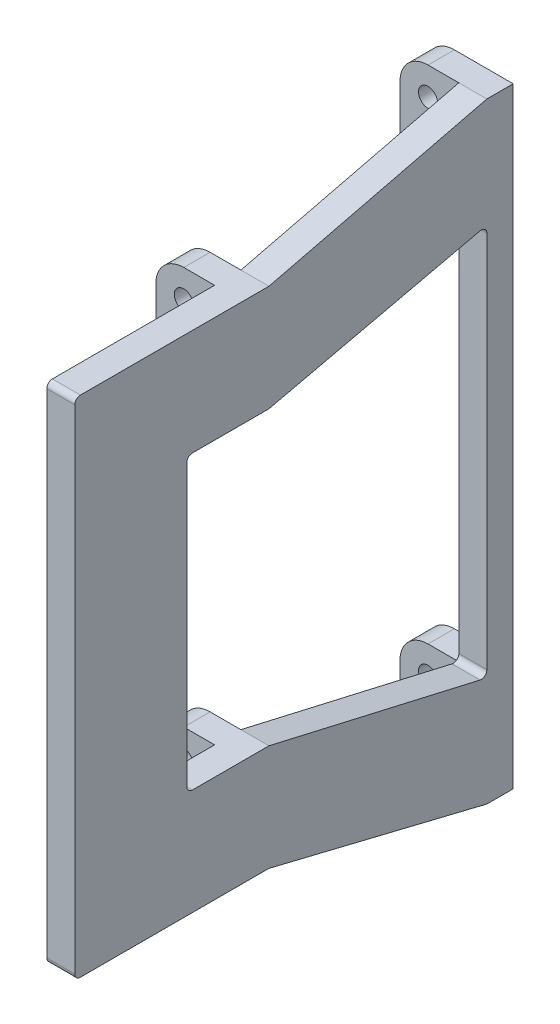
SolidWorks part; units mm, degrees
ref_plane "前基準面" through (0, 0, 0) normal (1, 0, 0) x (0, 1, 0)
ref_plane "上基準面" through (0, 0, 0) normal (0, 0, 1) x (0, 1, 0)
ref_plane "右基準面" through (0, 0, 0) normal (0, 1, 0) x (-1, 0, 0)
sketch "草圖1" plane through (0, 0, 0) normal (1, 0, 0) x (0, 1, 0)
  line L1 (-54.5, 39.125) -> (54.5, 39.125)
  line L2 (-54.5, 39.125) -> (-54.5, -39.125)
  line L3 (-54.5, -39.125) -> (54.5, -39.125)
  line L4 (54.5, 39.125) -> (54.5, -39.125)
  line L5 (-54.5, 39.125) -> (54.5, -39.125) construction
  line L6 (-54.5, -39.125) -> (54.5, 39.125) construction
  point P0 (0, 0)
  dimension "D1" = 78.25
  dimension "D2" = 109
extrude "填料-伸長1" add sketch "草圖1" along normal blind 5
sketch "草圖2" plane through (0, 0, 0) normal (-1, 0, 0) x (0, -1, 0)
  line L0 (-54.5, 39.125) -> (-54.5, -34.425)
  line L1 (-54.5, -39.125) -> (-54.5, 39.125) construction
  line L2 (-54.5, 39.125) -> (-45, 39.125)
  line L3 (-54.5, 39.125) -> (54.5, 39.125) construction
  line L4 (-45, 39.125) -> (-45, 4.475)
  line L5 (-45, 4.475) -> (-54.5, -34.425)
  line L6 (0, 39.125) -> (0, -39.125) construction
  line L7 (54.5, -39.125) -> (-54.5, -39.125) construction
  line L8 (45, 39.125) -> (45, 4.475)
  line L9 (54.5, 39.125) -> (45, 39.125)
  line L10 (54.5, 39.125) -> (54.5, -34.425)
  line L11 (45, 4.475) -> (54.5, -34.425)
  line L12 (-35, -34.425) -> (35, -34.425)
  line L13 (-26.05, 19.125) -> (26.05, 19.125)
  line L14 (-26.05, 19.125) -> (-26.05, 4.475)
  line L15 (26.05, 19.125) -> (26.05, 4.475)
  line L16 (-26.05, 4.475) -> (-35, -34.425)
  line L17 (26.05, 4.475) -> (35, -34.425)
  point P19 (0, -34.425)
  point P22 (0, 19.125)
  dimension "D1" = 73.55
  dimension "D2" = 9.5
  dimension "D3" = 34.65
  dimension "D4" = 70
  dimension "D5" = 4.7
  dimension "D6" = 52.1
  dimension "D7" = 20
  dimension "D8" = 14.65
  dimension "D9" = 14.65
extrude "除料-伸長1" cut sketch "草圖2" against normal blind 5
sketch "草圖3" plane through (0, 0, 0) normal (-1, 0, 0) x (0, -1, 0)
  line L0 (-26.05, 19.125) -> (-26.05, 4.475) construction
  line L1 (-45, 4.475) -> (-26.05, 4.475)
  line L2 (-45, 4.475) -> (-45, 9.175)
  line L3 (-45, 9.175) -> (-26.05, 9.175)
  line L4 (-26.05, 4.475) -> (-26.05, 9.175)
  line L5 (0, 39.125) -> (0, -39.125) construction
  line L6 (-54.5, -39.125) -> (-35, -39.125)
  line L7 (-54.5, -39.125) -> (-54.5, -34.425)
  line L8 (-54.5, -34.425) -> (-35, -34.425)
  line L9 (-35, -39.125) -> (-35, -34.425)
  line L10 (-45, 39.125) -> (45, 39.125) construction
  line L11 (54.5, -39.125) -> (-54.5, -39.125) construction
  line L12 (54.5, -34.425) -> (35, -34.425)
  line L13 (35, -39.125) -> (35, -34.425)
  line L14 (54.5, -39.125) -> (35, -39.125)
  line L15 (54.5, -39.125) -> (54.5, -34.425)
  line L16 (45, 9.175) -> (26.05, 9.175)
  line L17 (26.05, 4.475) -> (26.05, 9.175)
  line L18 (45, 4.475) -> (26.05, 4.475)
  line L19 (45, 4.475) -> (45, 9.175)
  dimension "D1" = 4.7
extrude "填料-伸長2" add sketch "草圖3" along normal blind 10.5
sketch "草圖4" plane through (0, 0, 9.175) normal (0, 0, 1) x (0, -1, 0)
  line L0 (-45, -10.5) -> (-45, 0) construction
  line L2 (-26.05, -10.5) -> (-45, -10.5) construction
  line L3 (-26.05, -10.5) -> (-26.05, 0) construction
  line L4 (0, 0) -> (0, 5) construction
  line L5 (-45, 5) -> (45, 5) construction
  line L8 (-31.05, -5.5) -> (-26.05, -5.5) construction
  line L11 (-26.05, 0) -> (-45, 0) construction
  line L12 (-31.05, -5.5) -> (-31.05, -10.5) construction
  line L13 (-31.05, -5.5) -> (-31.05, 0) construction
  circle A0 centre (-40, -5.5) radius 1.7
  circle A1 centre (-31.05, -5.5) radius 1.7
  circle A2 centre (31.05, -5.5) radius 1.7
  circle A3 centre (40, -5.5) radius 1.7
  dimension "D1" = 3.4
  dimension "D2" = 3.4
  dimension "D3" = 5
  dimension "D4" = 5
  dimension "D5" = 5
  dimension "D6" = 5
extrude "除料-伸長2" cut sketch "草圖4" against normal blind 5
sketch "草圖5" plane through (0, 0, -34.425) normal (0, 0, 1) x (0, -1, 0)
  line L0 (-54.5, -10.5) -> (-54.5, 0) construction
  line L1 (-35, -10.5) -> (-54.5, -10.5) construction
  line L2 (-35, -10.5) -> (-35, 0) construction
  line L3 (0, 0) -> (0, 5) construction
  line L4 (-35, 0) -> (35, 0) construction
  line L5 (-35, 5) -> (35, 5) construction
  circle A0 centre (-49.5, -5.5) radius 1.7
  circle A1 centre (-40, -5.5) radius 1.7
  circle A2 centre (40, -5.5) radius 1.7
  circle A3 centre (49.5, -5.5) radius 1.7
  point P6 (-54.5, -5.25)
  dimension "D5" = 3.4
  dimension "D6" = 3.4
  dimension "D1" = 5
  dimension "D2" = 5
  dimension "D3" = 5
  dimension "D4" = 5
extrude "除料-伸長3" cut sketch "草圖5" against normal blind 5
fillet "圓角1" radius 5 8 edges at (-10.5, 45, 6.825) (-10.5, 26.05, 6.825) (-10.5, -26.05, 6.825) (-10.5, -45, 6.825) (-10.5, -54.5, -36.775) (-10.5, -35, -36.775) (-10.5, 35, -36.775) (-10.5, 54.5, -36.775)
fillet "圓角2" radius 1 2 edges at (2.5, 45, 39.125) (2.5, -45, 39.125)
fillet "圓角3" radius 1 4 edges at (2.5, -35, -34.425) (2.5, 35, -34.425) (2.5, -26.05, 19.125) (2.5, 26.05, 19.125)
